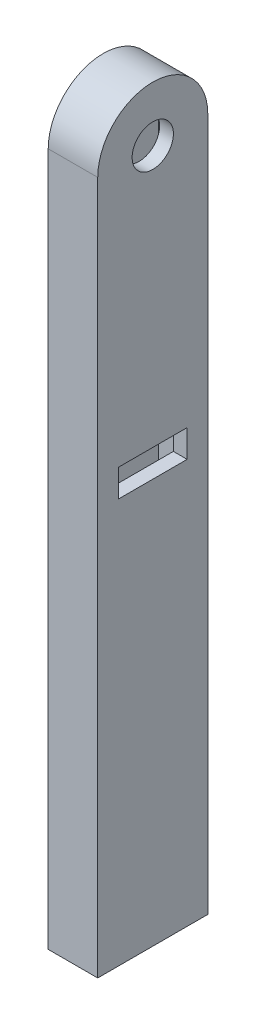
SolidWorks part; units mm, degrees
ref_plane "Front Plane" through (0, 0, 0) normal (0, 0, 1) x (1, 0, 0)
ref_plane "Top Plane" through (0, 0, 0) normal (0, 1, 0) x (1, 0, 0)
ref_plane "Right Plane" through (0, 0, 0) normal (1, 0, 0) x (0, 0, -1)
sketch "Sketch2" plane through (0, 0, 0) normal (1, 0, 0) x (0, 0, -1)
  line L0 (-20, 0) -> (20, 0) construction
  line L1 (-20, 0) -> (-20, -252)
  line L2 (20, 0) -> (20, -252)
  line L3 (0, 0) -> (0, 20) construction
  line L4 (-15, 0) -> (-15, -247)
  line L9 (-15, -247) -> (15, -247)
  line L10 (15, 0) -> (15, -247)
  line L11 (-20, -252) -> (20, -252) construction
  line L12 (0, 0) -> (0, -150) construction
  line L15 (-20, -252) -> (20, -252)
  line L19 (0, -150) -> (0, -239) construction
  line L20 (-20, -239) -> (20, -239) construction
  circle A0 centre (0, 0) radius 7.5
  circle A2 centre (0, -150) radius 10
  arc A7 (15, 0) -> (-15, 0) centre (0, 0) ccw
  arc A9 (20, 0) -> (-20, 0) centre (0, 0) ccw
  point P9 (9.3691, -243.7079)
  dimension "D1" = 15
  dimension "D7" = 20
  dimension "D2" = 40
  dimension "D3" = 5
  dimension "D4" = 252
  dimension "D5" = 13
  dimension "D6" = 150
sketch "Sketch3" plane through (0, 0, 0) normal (0, 0, 1) x (1, 0, 0)
  line L0 (-145.1347, 0) -> (145.1347, 0) construction
  line L1 (0, -164.4063) -> (0, 164.4063) construction
  line L2 (0, 0) -> (0, -252) construction
  point P3 (-4, 0)
  point P7 (-9, 0)
  point P12 (0, 0)
  dimension "D1" = 18
  dimension "D2" = 5
extrude "Boss-Extrude1" add sketch "Sketch2" along normal up to vertex (-4 mm away) from vertex contours L1 L15 L2 | A0 A2 | A2 region at (0, 17.2507, 0) region at (0, -119.045, 0) region at (0, -150, 0) up to point (-4, 0, 0) starting at point (-9, 0, 0)
extrude "Boss-Extrude2" add sketch "Sketch2<6>" along normal up to surface from vertex up to plane "Right Plane" starting at point (-4, 0, 0)
sketch "Sketch2<6>" plane through (0, 0, 0) normal (1, 0, 0) x (0, 0, -1) same geometry as "Sketch2"
mirror "Mirror1" about plane through (0, 0, 0) normal (1, 0, 0) of bodies 103
sketch "Sketch4" plane through (0, 0, 0) normal (1, 0, 0) x (0, 0, -1)
  line L0 (0, 0) -> (0, -150) construction
  line L1 (-12.5, -105) -> (12.5, -105)
  line L2 (-12.5, -105) -> (-12.5, -95)
  line L3 (-12.5, -95) -> (12.5, -95)
  line L4 (12.5, -105) -> (12.5, -95)
  line L5 (-12.5, -105) -> (12.5, -95) construction
  line L6 (-12.5, -95) -> (12.5, -105) construction
  point P0 (0, -100)
  dimension "D1" = 10
  dimension "D2" = 45
  dimension "D3" = 25
extrude "Cut-Extrude1" cut sketch "Sketch4" against normal up to next from surface starting at face at (9, -121, 0)
